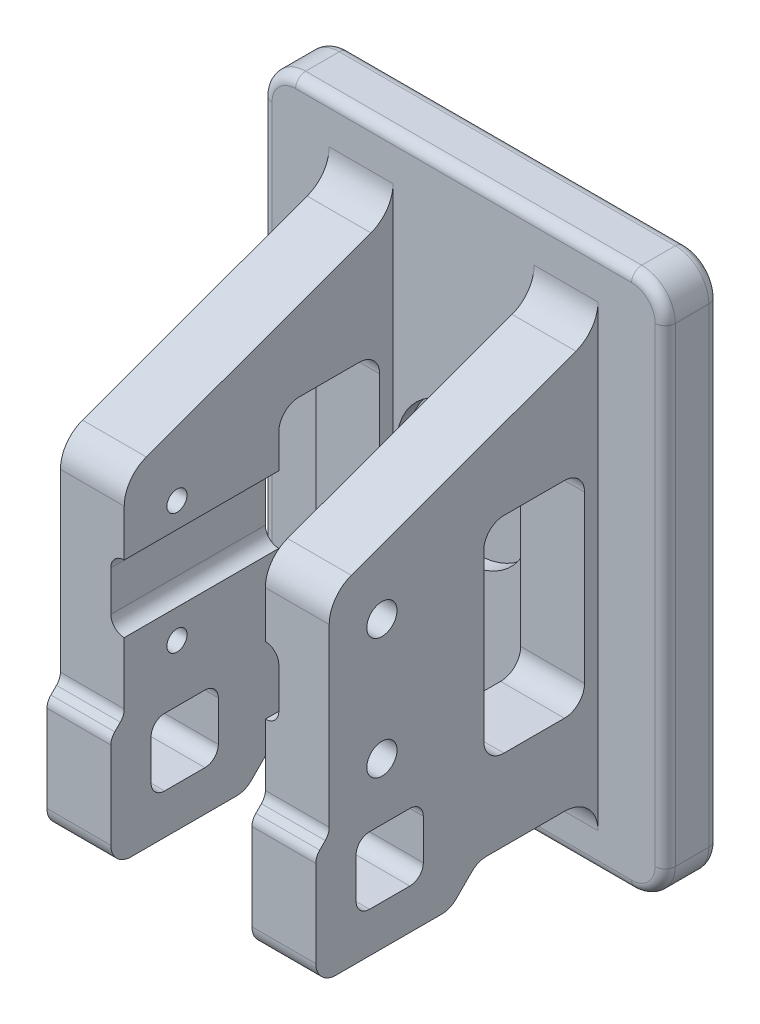
SolidWorks part; units mm, degrees
ref_plane "Front Plane" through (0, 0, 0) normal (0, 0, 1) x (1, 0, 0)
ref_plane "Top Plane" through (0, 0, 0) normal (0, 1, 0) x (1, 0, 0)
ref_plane "Right Plane" through (0, 0, 0) normal (1, 0, 0) x (0, 0, -1)
sketch "Sketch3" plane through (0, 0, 30) normal (0, 0, -1) x (-1, 0, 0)
  line L0 (95, 33.2573) -> (65, 33.2573) construction
  line L15 (80, 53.2573) -> (80, 33.2573) construction
  line L20 (55, 53.2573) -> (105, 53.2573)
  line L29 (55, -26.7427) -> (105, -26.7427)
  line L31 (110, -21.7427) -> (110, 48.2573)
  line L33 (50, -21.7427) -> (50, 48.2573)
  arc A17 (50, 48.2573) -> (55, 53.2573) centre (55, 48.2573) cw
  arc A18 (110, 48.2573) -> (105, 53.2573) centre (105, 48.2573) ccw
  arc A21 (50, -21.7427) -> (55, -26.7427) centre (55, -21.7427) ccw
  arc A22 (110, -21.7427) -> (105, -26.7427) centre (105, -21.7427) cw
  dimension "D1" = 5
extrude "Boss-Extrude1" add sketch "Sketch3" along normal blind 8
sketch "Sketch8" plane through (0, 0, 22) normal (0, 0, -1) x (-1, 0, 0)
  line L0 (50, 13.2573) -> (110, 13.2573) construction
  line L1 (50, 48.2573) -> (50, -21.7427) construction
  line L2 (110, -21.7427) -> (110, 48.2573) construction
  line L3 (80, 13.2573) -> (80, -26.7427) construction
  line L4 (55, -26.7427) -> (105, -26.7427) construction
  line L5 (78.25, 15.3786) -> (78.25, 11.136)
  line L6 (81.75, 15.3786) -> (81.75, 11.136)
  arc A0 (78.25, 11.136) -> (81.75, 11.136) centre (80, 13.2573) ccw
  arc A1 (81.75, 15.3786) -> (78.25, 15.3786) centre (80, 13.2573) ccw
extrude "Cut-Extrude3" cut sketch "Sketch8" against normal blind 3
sketch "Sketch10" plane through (0, 0, 22) normal (0, 0, -1) x (-1, 0, 0)
  line L0 (50, 13.2573) -> (110, 13.2573) construction
  line L1 (50, 48.2573) -> (50, -21.7427) construction
  line L2 (110, -21.7427) -> (110, 48.2573) construction
  line L3 (80, 13.2573) -> (80, -26.7427) construction
  line L4 (55, -26.7427) -> (105, -26.7427) construction
  line L7 (81.75, 11.136) -> (81.75, 15.3786)
  line L8 (78.25, 15.3786) -> (78.25, 11.136)
  line L9 (81.75, 11.136) -> (81.75, 15.3786)
  line L10 (78.25, 15.3786) -> (78.25, 11.136)
  circle A3 centre (80, 13.2573) radius 9.75
  arc A5 (78.25, 11.136) -> (81.75, 11.136) centre (80, 13.2573) ccw
  arc A6 (81.75, 15.3786) -> (78.25, 15.3786) centre (80, 13.2573) ccw
  arc A7 (78.25, 11.136) -> (81.75, 11.136) centre (80, 13.2573) ccw
  arc A8 (81.75, 15.3786) -> (78.25, 15.3786) centre (80, 13.2573) ccw
  dimension "D1" = 0
extrude "Boss-Extrude4" add sketch "Sketch10" along normal blind 9
fillet "Fillet2" radius 1.5 16 edges at (-80, -26.7427, 30) (-80, 53.2573, 30) (-50, 13.2573, 30) (-51.4645, 51.7928, 30) (-108.5355, 51.7928, 30) (-110, 13.2573, 30) (-80, -26.7427, 22) (-50, 13.2573, 22) (-51.4645, 51.7928, 22) (-80, 53.2573, 22) (-108.5355, 51.7928, 22) (-110, 13.2573, 22) (-108.5355, -25.2783, 22) (-51.4645, -25.2783, 22) (-108.5355, -25.2783, 30) (-51.4645, -25.2783, 30)
sketch "Sketch11" plane through (0, 0, 22) normal (0, 0, -1) x (-1, 0, 0)
  line L0 (50, 13.2573) -> (110, 13.2573) construction
  line L1 (50, -21.7427) -> (50, 48.2573) construction
  line L2 (110, 48.2573) -> (110, -21.7427) construction
  line L3 (80, 13.2573) -> (80, -26.7427) construction
  line L4 (105, -26.7427) -> (55, -26.7427) construction
  circle A0 centre (80, 13.2573) radius 11.75
extrude "Boss-Extrude5" add sketch "Sketch11" along normal blind 1
sketch "Sketch14" plane through (-70, 0, 0) normal (1, 0, 0) x (0, 0, -1)
  line L0 (-22, 1.5073) -> (-22, 25.0073) construction
  line L1 (-30, 48.2573) -> (-30, -21.7427) construction
  line L2 (-70, -1.7605) -> (-70, 28.6985)
  line L3 (-70, 28.6985) -> (-30, 43.2573)
  line L4 (-30, -16.3789) -> (-47.8764, -16.3789)
  line L6 (-30, -16.3789) -> (-30, 43.2573)
  line L7 (-47.8764, -16.3789) -> (-52, -20.5025)
  line L8 (-52, -20.5025) -> (-72, -20.5025)
  line L9 (-72, -20.5025) -> (-72, -3.7605)
  line L11 (-72, -3.7605) -> (-70, -1.7605)
  circle A6 centre (-62.1572, 3.9815) radius 1.5 construction
  circle A7 centre (-62.1572, 21.9815) radius 1.5 construction
  circle A8 centre (-62.1572, 3.9815) radius 1.5
  circle A9 centre (-62.1572, 21.9815) radius 1.5
extrude "Boss-Extrude7" add sketch "Sketch14" along normal blind 10
sketch "Sketch15" plane through (-90, 0, 0) normal (-1, 0, 0) x (0, 0, 1)
  line L4 (47.8764, -16.3789) -> (52, -20.5025)
  line L5 (70, -1.7605) -> (70, 28.6985)
  line L6 (70, 28.6985) -> (30, 43.2573)
  line L7 (30, 43.2573) -> (30, -16.3789)
  line L9 (70, -1.7605) -> (70, 28.6985)
  line L10 (70, 28.6985) -> (30, 43.2573)
  line L15 (30, 43.2573) -> (30, -16.3789)
  line L20 (47.8764, -16.3789) -> (52, -20.5025)
  line L21 (52, -20.5025) -> (72, -20.5025)
  line L22 (52, -20.5025) -> (72, -20.5025)
  line L23 (72, -20.5025) -> (72, -3.7605)
  line L24 (72, -20.5025) -> (72, -3.7605)
  line L25 (72, -3.7605) -> (70, -1.7605)
  line L26 (72, -3.7605) -> (70, -1.7605)
  line L27 (30, -16.3789) -> (47.8764, -16.3789)
  line L28 (30, -16.3789) -> (47.8764, -16.3789)
  circle A2 centre (62.1572, 3.9815) radius 1.5 construction
  circle A3 centre (62.1572, 21.9815) radius 1.5 construction
  circle A4 centre (62.1572, 3.9815) radius 1.5
  circle A5 centre (62.1572, 21.9815) radius 1.5
  dimension "D1" = 0
extrude "Boss-Extrude8" add sketch "Sketch15" along normal blind 10
fillet "Fillet3" radius 5 6 edges at (-65, 43.2573, 30) (-95, 43.2573, 30) (-95, 28.6985, 70) (-65, 28.6985, 70) (-95, -16.3789, 30) (-65, -16.3789, 30)
fillet "Fillet4" radius 3 6 edges at (-95, -20.5025, 72) (-65, -20.5025, 72) (-65, -20.5025, 52) (-95, -20.5025, 52) (-95, -16.3789, 47.8764) (-65, -16.3789, 47.8764)
sketch "Sketch16" plane through (-90, 0, 0) normal (1, 0, 0) x (0, 0, -1)
  line L8 (-72, -3.7605) -> (-72, -17.5025)
  line L9 (-69, -20.5025) -> (-53.2426, -20.5025)
  line L10 (-51.1213, -19.6238) -> (-48.7551, -17.2576)
  line L11 (-46.6337, -16.3789) -> (-35, -16.3789)
  line L12 (-30, -21.3789) -> (-30, 46.7583)
  line L13 (-33.2899, 42.0599) -> (-66.7101, 29.8959)
  line L14 (-70, 25.1974) -> (-70, -1.7605)
  line L15 (-70, -1.7605) -> (-72, -3.7605)
  line L16 (-72, -3.7605) -> (-72, -17.5025)
  line L17 (-69, -20.5025) -> (-53.2426, -20.5025)
  line L18 (-51.1213, -19.6238) -> (-48.7551, -17.2576)
  line L19 (-46.6337, -16.3789) -> (-35, -16.3789)
  line L20 (-30, -21.3789) -> (-30, 46.7583)
  line L21 (-33.2899, 42.0599) -> (-66.7101, 29.8959)
  line L22 (-70, 25.1974) -> (-70, -1.7605)
  line L23 (-70, -1.7605) -> (-72, -3.7605)
  arc A6 (-72, -17.5025) -> (-69, -20.5025) centre (-69, -17.5025) ccw
  arc A7 (-53.2426, -20.5025) -> (-51.1213, -19.6238) centre (-53.2426, -17.5025) ccw
  arc A8 (-46.6337, -16.3789) -> (-48.7551, -17.2576) centre (-46.6337, -19.3789) ccw
  arc A9 (-30, -21.3789) -> (-35, -16.3789) centre (-35, -21.3789) ccw
  arc A10 (-33.2899, 42.0599) -> (-30, 46.7583) centre (-35, 46.7583) ccw
  arc A11 (-66.7101, 29.8959) -> (-70, 25.1974) centre (-65, 25.1974) ccw
  arc A12 (-72, -17.5025) -> (-69, -20.5025) centre (-69, -17.5025) ccw
  arc A13 (-53.2426, -20.5025) -> (-51.1213, -19.6238) centre (-53.2426, -17.5025) ccw
  arc A14 (-46.6337, -16.3789) -> (-48.7551, -17.2576) centre (-46.6337, -19.3789) ccw
  arc A15 (-30, -21.3789) -> (-35, -16.3789) centre (-35, -21.3789) ccw
  arc A16 (-33.2899, 42.0599) -> (-30, 46.7583) centre (-35, 46.7583) ccw
  arc A17 (-66.7101, 29.8959) -> (-70, 25.1974) centre (-65, 25.1974) ccw
  dimension "D1" = 0
extrude "Cut-Extrude4" cut sketch "Sketch16" against normal blind 0.25
sketch "Sketch17" plane through (-70, 0, 0) normal (-1, 0, 0) x (0, 0, 1)
  line L8 (53.2426, -20.5025) -> (69, -20.5025)
  line L9 (72, -17.5025) -> (72, -3.7605)
  line L10 (72, -3.7605) -> (70, -1.7605)
  line L11 (70, -1.7605) -> (70, 25.1974)
  line L12 (66.7101, 29.8959) -> (33.2899, 42.0599)
  line L13 (30, 46.7583) -> (30, -21.3789)
  line L14 (35, -16.3789) -> (46.6337, -16.3789)
  line L15 (48.7551, -17.2576) -> (51.1213, -19.6238)
  line L16 (53.2426, -20.5025) -> (69, -20.5025)
  line L17 (72, -17.5025) -> (72, -3.7605)
  line L18 (72, -3.7605) -> (70, -1.7605)
  line L19 (70, -1.7605) -> (70, 25.1974)
  line L20 (66.7101, 29.8959) -> (33.2899, 42.0599)
  line L21 (30, 46.7583) -> (30, -21.3789)
  line L22 (35, -16.3789) -> (46.6337, -16.3789)
  line L23 (48.7551, -17.2576) -> (51.1213, -19.6238)
  arc A6 (69, -20.5025) -> (72, -17.5025) centre (69, -17.5025) ccw
  arc A7 (70, 25.1974) -> (66.7101, 29.8959) centre (65, 25.1974) ccw
  arc A8 (30, 46.7583) -> (33.2899, 42.0599) centre (35, 46.7583) ccw
  arc A9 (35, -16.3789) -> (30, -21.3789) centre (35, -21.3789) ccw
  arc A10 (48.7551, -17.2576) -> (46.6337, -16.3789) centre (46.6337, -19.3789) ccw
  arc A11 (51.1213, -19.6238) -> (53.2426, -20.5025) centre (53.2426, -17.5025) ccw
  arc A12 (69, -20.5025) -> (72, -17.5025) centre (69, -17.5025) ccw
  arc A13 (70, 25.1974) -> (66.7101, 29.8959) centre (65, 25.1974) ccw
  arc A14 (30, 46.7583) -> (33.2899, 42.0599) centre (35, 46.7583) ccw
  arc A15 (35, -16.3789) -> (30, -21.3789) centre (35, -21.3789) ccw
  arc A16 (48.7551, -17.2576) -> (46.6337, -16.3789) centre (46.6337, -19.3789) ccw
  arc A17 (51.1213, -19.6238) -> (53.2426, -20.5025) centre (53.2426, -17.5025) ccw
  dimension "D1" = 0
extrude "Cut-Extrude5" cut sketch "Sketch17" against normal blind 0.25
sketch "Sketch18" plane through (-100, 0, 0) normal (-1, 0, 0) x (0, 0, 1)
  line L0 (23.5, 53.2573) -> (28.5, 53.2573) construction
  line L1 (35, 26.2573) -> (44, 26.2573)
  line L2 (32, 23.2573) -> (32, -1.3789)
  line L3 (35, -4.3789) -> (44, -4.3789)
  line L4 (47, 23.2573) -> (47, -1.3789)
  line L5 (35, -16.3789) -> (46.6337, -16.3789) construction
  line L6 (30, 48.2573) -> (30, -21.7427) construction
  line L7 (53.2426, -20.5025) -> (69, -20.5025) construction
  line L8 (64, -14.5025) -> (58, -14.5025)
  line L9 (66, -12.5025) -> (66, -6.5025)
  line L10 (64, -4.5025) -> (58, -4.5025)
  line L11 (56, -12.5025) -> (56, -6.5025)
  line L12 (72, -17.5025) -> (72, -3.7605) construction
  arc A0 (44, -4.3789) -> (47, -1.3789) centre (44, -1.3789) ccw
  arc A1 (32, -1.3789) -> (35, -4.3789) centre (35, -1.3789) ccw
  arc A2 (35, 26.2573) -> (32, 23.2573) centre (35, 23.2573) ccw
  arc A3 (44, 26.2573) -> (47, 23.2573) centre (44, 23.2573) cw
  arc A4 (66, -6.5025) -> (64, -4.5025) centre (64, -6.5025) ccw
  arc A5 (64, -14.5025) -> (66, -12.5025) centre (64, -12.5025) ccw
  arc A6 (58, -14.5025) -> (56, -12.5025) centre (58, -12.5025) cw
  arc A7 (58, -4.5025) -> (56, -6.5025) centre (58, -6.5025) ccw
  point P16 (32, 26.2573)
  point P19 (47, 26.2573)
  point P30 (66, -4.5025)
  point P33 (66, -14.5025)
  point P38 (56, -4.5025)
  dimension "D5" = 3
  dimension "D10" = 2
  dimension "D1" = 27
  dimension "D2" = 12
  dimension "D3" = 15
  dimension "D4" = 2
  dimension "D6" = 6
  dimension "D7" = 6
  dimension "D8" = 10
  dimension "D9" = 10
extrude "Cut-Extrude6" cut sketch "Sketch18" against normal up to surface (40 mm away) up to face at (-60, -0.7658, 53.3813)
sketch "Sketch19" plane through (-60, 0, 0) normal (1, 0, 0) x (0, 0, -1)
  circle A0 centre (-62.1572, 21.9815) radius 2.25
  circle A1 centre (-62.1572, 3.9815) radius 2.25
extrude "Cut-Extrude7" cut sketch "Sketch19" against normal blind 4
chamfer "Chamfer1" distance 1.5 angle 45 2 edges at (-100, 2.4815, 62.1572) (-100, 20.4815, 62.1572)
sketch "Sketch20" plane through (0, 0, 72) normal (0, 0, 1) x (1, 0, 0)
  line L0 (-105, 53.2573) -> (-55, 53.2573) construction
  line L1 (-90.5, 53.2573) -> (-69.5, 53.2573)
  line L2 (-90.5, 53.2573) -> (-90.5, -26.7427)
  line L3 (-90.5, -26.7427) -> (-69.5, -26.7427)
  line L4 (-69.5, 53.2573) -> (-69.5, -26.7427)
  line L5 (-55, -26.7427) -> (-105, -26.7427) construction
  line L6 (-69.75, 46.7583) -> (-69.75, 42.0599) construction
  line L7 (-90.25, 42.0599) -> (-90.25, 29.8959) construction
  dimension "D1" = 0.25
  dimension "D2" = 0.25
extrude "Cut-Extrude8" cut sketch "Sketch20" against normal up to surface (42 mm away) up to face at (-95.125, 12.6897, 30)
fillet "Fillet5" radius 2 4 edges at (-95.25, -3.7605, 72) (-95.25, -1.7605, 70) (-64.75, -3.7605, 72) (-64.75, -1.7605, 70)
sketch "Sketch21" plane through (0, 0, 21) normal (0, 0, -1) x (-1, 0, 0)
  line L2 (81.75, 11.136) -> (81.75, 15.3786)
  line L3 (78.25, 15.3786) -> (78.25, 11.136)
  line L4 (81.75, 11.136) -> (81.75, 15.3786)
  line L5 (78.25, 15.3786) -> (78.25, 11.136)
  arc A2 (81.75, 15.3786) -> (78.25, 15.3786) centre (80, 13.2573) ccw
  arc A3 (78.25, 11.136) -> (81.75, 11.136) centre (80, 13.2573) ccw
  arc A4 (81.75, 15.3786) -> (78.25, 15.3786) centre (80, 13.2573) ccw
  arc A5 (78.25, 11.136) -> (81.75, 11.136) centre (80, 13.2573) ccw
  dimension "D1" = 0
extrude "Cut-Extrude9" cut sketch "Sketch21" against normal blind 5
sketch "Sketch22" plane through (0, 0, 30) normal (0, 0, 1) x (1, 0, 0)
  line L0 (-110, 13.2573) -> (-80, 13.2573) construction
  line L1 (-110, -21.7427) -> (-110, 48.2573) construction
  line L2 (-80, 13.2573) -> (-80, 53.2573) construction
  line L3 (-105, 53.2573) -> (-55, 53.2573) construction
  circle A0 centre (-80, 13.2573) radius 10
extrude "Cut-Extrude10" cut sketch "Sketch22" against normal blind 2
sketch "Sketch23" plane through (0, 0, 70) normal (0, 0, 1) x (1, 0, 0)
  line L0 (-90, 13.2573) -> (-70, 13.2573) construction
  line L1 (-90.5, -0.9321) -> (-90.5, 25.1974) construction
  line L2 (-90.5, 18.2573) -> (-92.5, 18.2573)
  line L3 (-90.5, 18.2573) -> (-90.5, 8.2573)
  line L4 (-90.5, 8.2573) -> (-92.5, 8.2573)
  line L5 (-92.5, 18.2573) -> (-92.5, 8.2573)
  line L6 (-69.5, 25.1974) -> (-69.5, -0.9321) construction
  line L7 (-69.5, 18.2573) -> (-67.5, 18.2573)
  line L8 (-69.5, 18.2573) -> (-69.5, 8.2573)
  line L9 (-69.5, 8.2573) -> (-67.5, 8.2573)
  line L10 (-67.5, 18.2573) -> (-67.5, 8.2573)
  circle A0 centre (-80, 13.2573) radius 10 construction
  dimension "D1" = 5
  dimension "D2" = 10
  dimension "D3" = 10
  dimension "D4" = 5
  dimension "D5" = 2
  dimension "D6" = 2
extrude "Cut-Extrude11" cut sketch "Sketch23" against normal up to surface (38 mm away) up to face at (-64.75, 10.9392, 32)
fillet "Fillet6" radius 2 4 edges at (-92.5, 8.2573, 58.5) (-92.5, 18.2573, 58.5) (-67.5, 8.2573, 58.5) (-67.5, 18.2573, 58.5)
